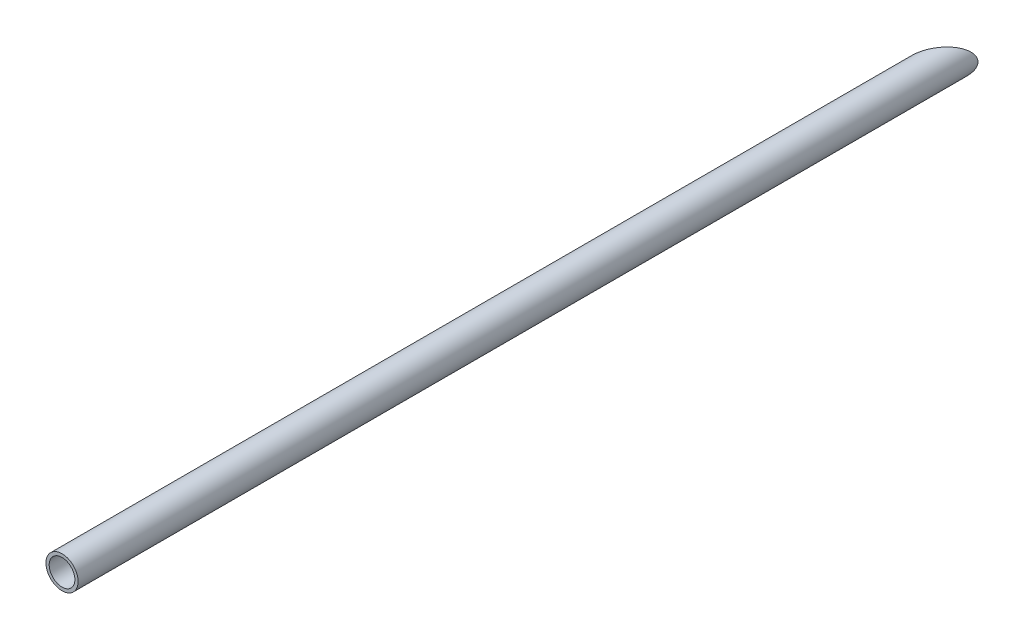
SolidWorks part; units mm, degrees
ref_plane "Front Plane" through (0, 0, 0) normal (0, 0, 1) x (1, 0, 0)
ref_plane "Top Plane" through (0, 0, 0) normal (0, 1, 0) x (1, 0, 0)
ref_plane "Right Plane" through (0, 0, 0) normal (1, 0, 0) x (0, 0, -1)
sketch "Sketch1" plane through (0, 0, 0) normal (0, 0, 1) x (1, 0, 0)
  circle A0 centre (0, 0) radius 15.875
  circle A1 centre (0, 0) radius 12.7
  dimension "D1" = 31.75
  dimension "D2" = 3.175
extrude "Boss-Extrude1" add sketch "Sketch1" along normal blind 889
ref_axis "Axis1" through (0, 0, 889) along (0, 0, -1)
sketch "Sketch3" plane through (0, 0, 0) normal (0, 1, 0) x (1, 0, 0)
  line L0 (0, 0) -> (15.875, 0)
  line L1 (15.875, 0) -> (-47.625, -90.6874)
  line L2 (15.875, -889) -> (15.875, 0) construction
  line L3 (0, 0) -> (-47.625, 0)
  line L4 (-47.625, 0) -> (-47.625, -90.6874)
  line L5 (0, -889) -> (0, 0) construction
  point P3 (0, -22.6718)
  dimension "D1" = 55
  dimension "D2" = 63.5
extrude "Cut-Extrude1" cut sketch "Sketch3" against normal through all both and the other way through all
